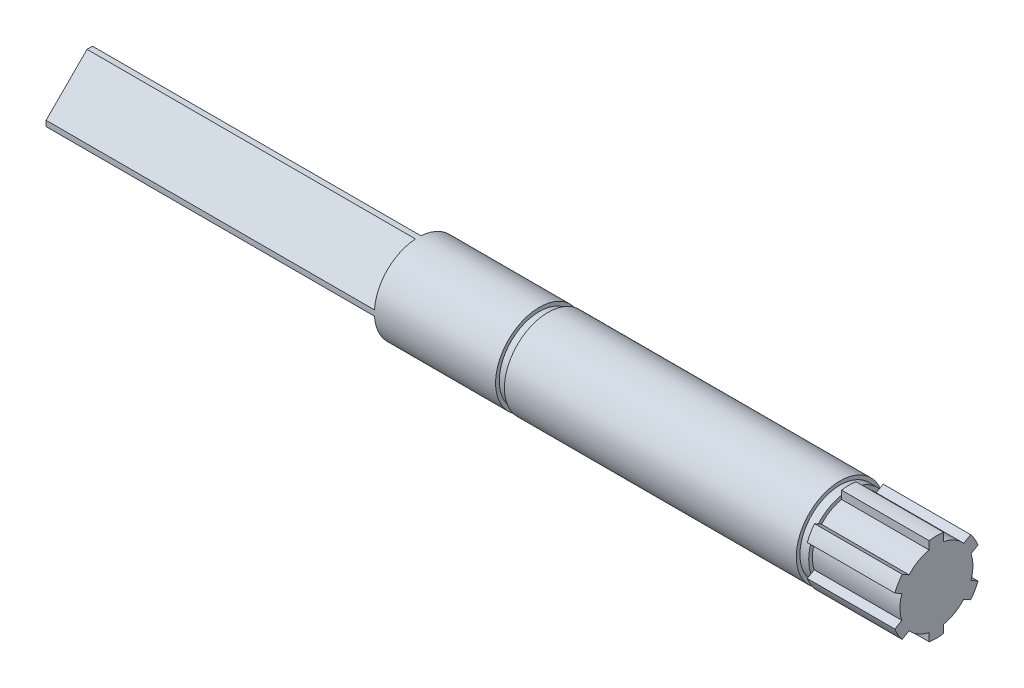
SolidWorks part; units mm, degrees
ref_plane "前视基准面" through (0, 0, 0) normal (0, 0, 1) x (1, 0, 0)
ref_plane "上视基准面" through (0, 0, 0) normal (0, 1, 0) x (1, 0, 0)
ref_plane "右视基准面" through (0, 0, 0) normal (1, 0, 0) x (0, 0, -1)
other "Configuration Table"
ref_axis "基准轴1" through (88.99, 0, 0) along (-1, 0, 0)
sketch "草图1" plane through (0, 0, 0) normal (1, 0, 0) x (0, 0, -1)
  line L1 (6.364, 0) -> (0, 6.364)
  line L2 (0, 6.364) -> (-6.364, 0)
  line L3 (-6.364, 0) -> (0, -6.364)
  line L4 (0, -6.364) -> (6.364, 0)
  circle A0 centre (0, 0) radius 4.5 construction
extrude "凸台-拉伸1" add sketch "草图1" along normal blind 45
sketch "草图2" plane through (45, 0, 0) normal (1, 0, 0) x (0, 0, -1)
  circle A0 centre (0, 0) radius 6
extrude "凸台-拉伸2" add sketch "草图2" along normal blind 16.6
sketch "草图3" plane through (61.6, 0, 0) normal (1, 0, 0) x (0, 0, -1)
  circle A0 centre (0, 0) radius 5.5
extrude "凸台-拉伸3" add sketch "草图3" along normal blind 1.2
sketch "草图4" plane through (62.8, 0, 0) normal (1, 0, 0) x (0, 0, -1)
  circle A0 centre (0, 0) radius 6
extrude "凸台-拉伸4" add sketch "草图4" along normal blind 40
sketch "草图5" plane through (102.8, 0, 0) normal (1, 0, 0) x (0, 0, -1)
  circle A0 centre (0, 0) radius 5.5
extrude "凸台-拉伸5" add sketch "草图5" along normal blind 1.2
sketch "草图6" plane through (104, 0, 0) normal (1, 0, 0) x (0, 0, -1)
  circle A0 centre (0, 0) radius 7
extrude "凸台-拉伸6" add sketch "草图6" along normal blind 12
sketch "草图7" plane through (116, 0, 0) normal (1, 0, 0) x (0, 0, -1)
  line L0 (1, 6) -> (1, 4.899)
  line L1 (-1, 6) -> (-1, 4.899)
  line L2 (5, 8.6603) -> (2.5, 4.3301)
  line L3 (-5, 8.6603) -> (-2.5, 4.3301)
  arc A0 (-2.5, 4.3301) -> (-1, 4.899) centre (0, 0) cw
  arc A1 (1, 4.899) -> (2.5, 4.3301) centre (0, 0) cw
  arc A2 (-5, 8.6603) -> (5, 8.6603) centre (0, 0) cw
  arc A3 (1, 6) -> (-1, 6) centre (0, 0) ccw
extrude "切除-拉伸1" cut sketch "草图7" against normal blind 12
pattern_circular "阵列(圆周)1" count 6 every 60 about axis through (88.99, 0, 0) along (-1, 0, 0) of "切除-拉伸1"
ref_plane "基准面1" through (45, 0.3757, 5.9882) normal (0, -0.7071, 0.7071) x (-1, 0, 0)
sketch "草图9" plane through (45, 0, 0) normal (-1, 0, 0) x (0, 0, 1)
  circle A0 centre (0, 0) radius 6
extrude "切除-拉伸2" cut sketch "草图9" along normal through all flip side to cut
sketch "草图10" plane through (0, 0, 0) normal (-1, 0, 0) x (0, 0, 1)
  circle A0 centre (0, 0) radius 1.1199
sketch "草图13" plane through (0, 0, 0) normal (-1, 0, 0) x (0, 0, 1)
  circle A0 centre (0, 0) radius 1.2993
extrude "切除-拉伸3" cut sketch "草图13" against normal blind 12
